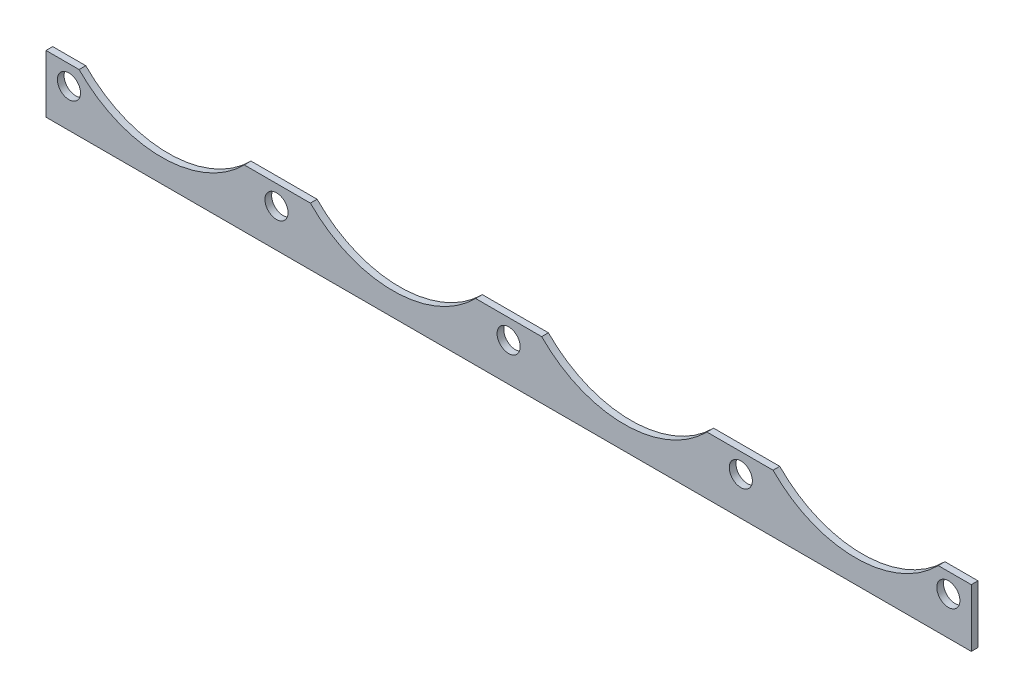
SolidWorks part; units mm, degrees
ref_plane "Front Plane" through (0, 0, 0) normal (0, 0, 1) x (1, 0, 0)
ref_plane "Top Plane" through (0, 0, 0) normal (0, 1, 0) x (1, 0, 0)
ref_plane "Right Plane" through (0, 0, 0) normal (1, 0, 0) x (0, 0, -1)
sketch "Sketch1" plane through (0, 0, 0) normal (0, 0, 1) x (1, 0, 0)
  line L0 (0, 12.7) -> (0, 0) construction
  line L1 (-101.6, 12.7) -> (101.6, 12.7)
  line L2 (-101.6, 12.7) -> (-101.6, 0)
  line L3 (-101.6, 0) -> (101.6, 0)
  line L4 (101.6, 12.7) -> (101.6, 0)
  circle A0 centre (-76.2, 30.48) radius 25.4
  circle A1 centre (-25.4, 30.48) radius 25.4
  circle A2 centre (25.4, 30.48) radius 25.4
  circle A3 centre (76.2, 30.48) radius 25.4
  circle A4 centre (-96.562, 8.3989) radius 2.54
  circle A5 centre (-50.9847, 8.3989) radius 2.54
  circle A6 centre (96.562, 8.3989) radius 2.54
  circle A7 centre (0, 8.3989) radius 2.54
  circle A8 centre (50.9847, 8.3989) radius 2.54
  dimension "D3" = 50.8
  dimension "D4" = 4
  dimension "D5" = 30.48
  dimension "D6" = 3
  dimension "D1" = 203.2
  dimension "D2" = 12.7
extrude "Boss-Extrude1" add sketch "Sketch1" along normal mid plane 1.4732 contours L0 L1 A1 A0 L2 L3 A7 A4 A5 | L1 L0 A7 L3 L4 A3 A2 A6 A8 region at (50.3021, 4.7814, 0) region at (-50.3021, 4.7814, 0)
